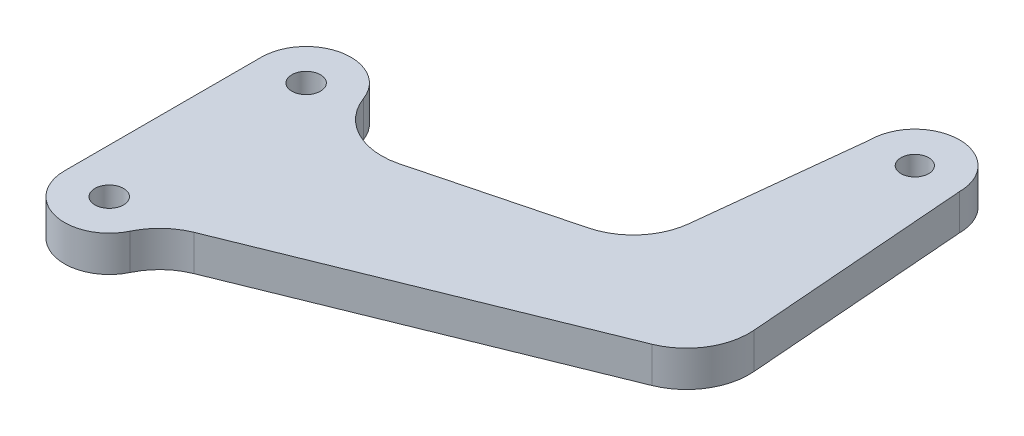
SolidWorks part; units mm, degrees
ref_plane "Front Plane" through (0, 0, 0) normal (0, 0, 1) x (1, 0, 0)
ref_plane "Top Plane" through (0, 0, 0) normal (0, 1, 0) x (1, 0, 0)
ref_plane "Right Plane" through (0, 0, 0) normal (1, 0, 0) x (0, 0, -1)
sketch "Sketch1" plane through (0, 0, 0) normal (0, 1, 0) x (1, 0, 0)
  line L5 (5, 11) -> (-5, 11)
  line L6 (5, 11) -> (5, -11)
  line L7 (5, -11) -> (-5, -11)
  line L8 (-5, 11) -> (-5, -11)
  line L9 (5, 11) -> (-5, -11) construction
  line L10 (5, -11) -> (-5, 11) construction
  circle A0 centre (0, 11) radius 1.6
  circle A1 centre (0, -11) radius 1.6
  circle A2 centre (0, 11) radius 5
  circle A7 centre (0, -11) radius 5
  point P0 (0, 0)
  point P1 (0, 0)
  dimension "D1" = 3.2
  dimension "D2" = 3.2
  dimension "D6" = 10
  dimension "D3" = 22
  dimension "D4" = 11
extrude "Boss-Extrude1" add sketch "Sketch1" along normal blind 2 and the other way blind 2 contours A2 | L7 A2 A0 | L7 A2 A0 | A1 | A1 region at (0, 0, -8.7133) region at (0, 0, -13.2867) region at (0, 0, 0) region at (0, 0, 13.2867) region at (0, 0, 8.7133)
sketch "Sketch3" plane through (0, 0, 0) normal (0, 1, 0) x (1, 0, 0)
  line L0 (5, 6.3057) -> (34.4684, 13.9542)
  line L1 (37, 37) -> (34.4684, 13.9542)
  line L2 (47, 37) -> (49.3345, 6.9666)
  line L3 (49.3345, 6.9666) -> (5, -11)
  line L4 (5, 6.3057) -> (5, -11)
  line L5 (5, 11) -> (5, -11) construction
  circle A1 centre (42, 37) radius 5
  circle A4 centre (42, 37) radius 1.55
  point P0 (34.4684, 13.9542)
  dimension "D1" = 3.1
  dimension "D4" = 42
  dimension "D2" = 10
  dimension "D3" = 37
extrude "Boss-Extrude3" add sketch "Sketch3" along normal blind 2 and the other way blind 2 contours L1 L0 L4 L3 L2 | A1 | A1 | A4 region at (29.4757, 0, -9.4697)
fillet "Fillet1" radius 7 4 edges at (5, 0, 11) (49.3345, 0, -6.9666) (34.4684, 0, -13.9542) (5, 0, -6.3057)
